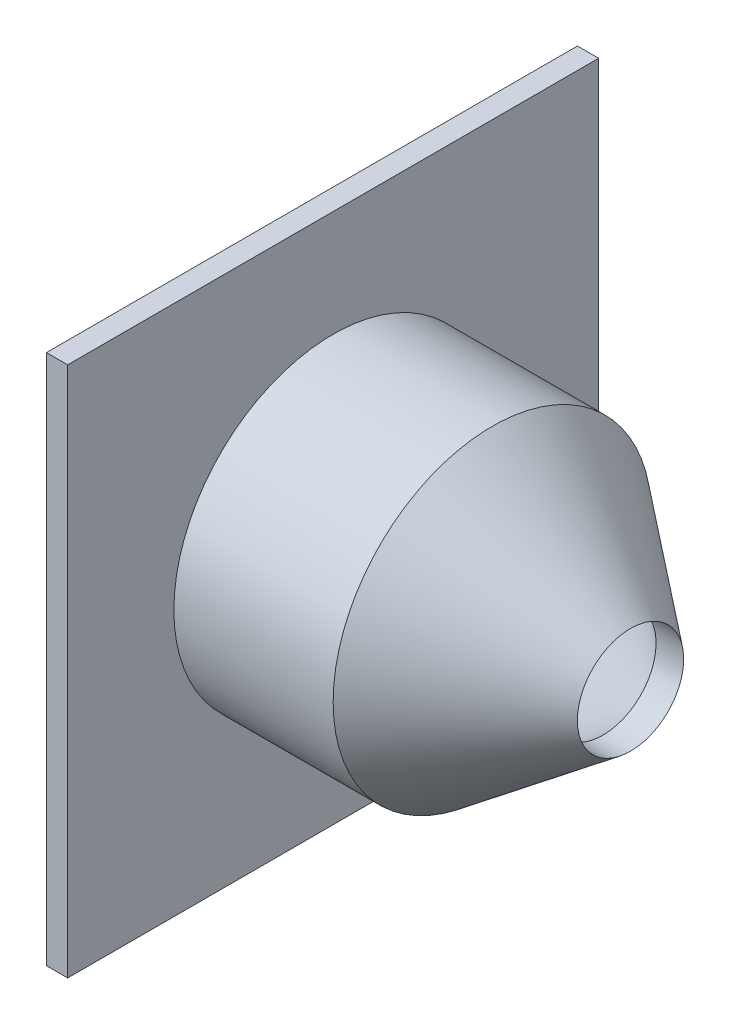
SolidWorks part; units mm, degrees
ref_plane "Front Plane" through (0, 0, 0) normal (0, 0, 1) x (1, 0, 0)
ref_plane "Top Plane" through (0, 0, 0) normal (0, 1, 0) x (1, 0, 0)
ref_plane "Right Plane" through (0, 0, 0) normal (1, 0, 0) x (0, 0, -1)
sketch "Sketch1" plane through (0, 0, 0) normal (1, 0, 0) x (0, 0, -1)
  line L1 (-25, 25) -> (25, 25)
  line L2 (-25, 25) -> (-25, -25)
  line L3 (-25, -25) -> (25, -25)
  line L4 (25, 25) -> (25, -25)
  line L5 (-25, 25) -> (25, -25) construction
  line L6 (-25, -25) -> (25, 25) construction
  circle A0 centre (0, 0) radius 15
  circle A1 centre (0, 0) radius 13
  point P2 (0, 0)
  dimension "D1" = 50
  dimension "D3" = 30
  dimension "D2" = 50
extrude "Boss-Extrude1" add sketch "Sketch1" along normal blind 17 contours A0 A1 region at (0, 0, 14.5757)
extrude "Boss-Extrude2" add sketch "Sketch1<4>" along normal blind 2 separate body contours L4 L1 L2 L3 A0 region at (0, 24.2929, 0)
sketch "Sketch1<4>" plane through (0, 0, 0) normal (1, 0, 0) x (0, 0, -1) same geometry as "Sketch1"
sketch "Sketch5" plane through (0, 0, 0) normal (0, 1, 0) x (1, 0, 0)
  line L0 (17, 15) -> (30, 5.0063)
  line L1 (17, 13) -> (27.3983, 5.0063)
  line L2 (27.3983, 5.0063) -> (30, 5.0063)
  line L3 (17, 13) -> (17, 15)
  line L4 (-1.322, 0) -> (30.7907, 0)
  point P9 (0, 0)
revolve "Revolve1" add sketch "Sketch5" angle 360 about L4
